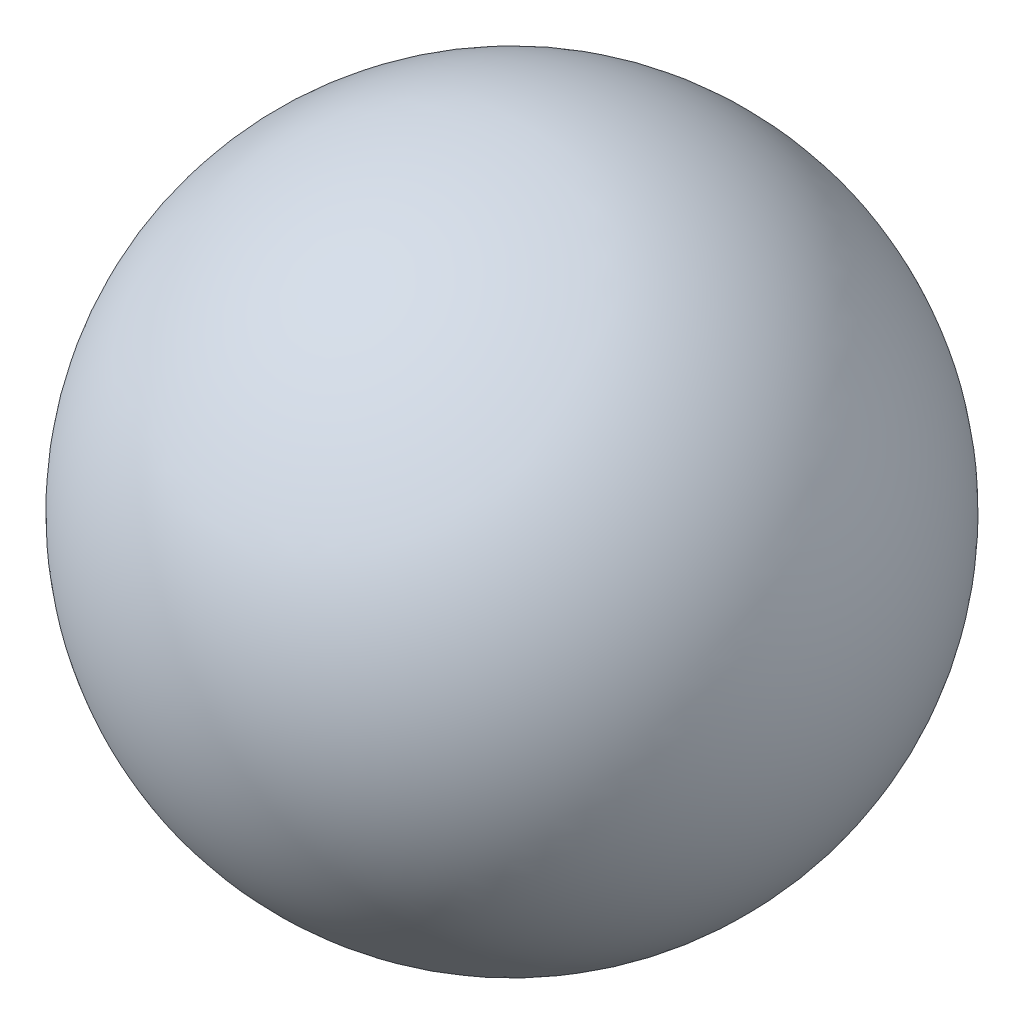
SolidWorks part; units mm, degrees
ref_plane "Plano frontal" through (0, 0, 0) normal (0, 0, 1) x (1, 0, 0)
ref_plane "Plano superior" through (0, 0, 0) normal (0, 1, 0) x (1, 0, 0)
ref_plane "Plano direito" through (0, 0, 0) normal (1, 0, 0) x (0, 0, -1)
sketch "Esboço1" plane through (0, 0, 0) normal (0, 1, 0) x (1, 0, 0)
  line L0 (0, 3.6028) -> (0, -5.4663) construction
  line L1 (0, 2.25) -> (0, -2.25)
  arc A0 (0, -2.25) -> (0, 2.25) centre (0, 0) ccw
revolve "Revolução1" add sketch "Esboço1" angle 360 about L0
ref_plane "Plano1" through (0, 1.75, 0) normal (0, 1, 0) x (1, 0, 0)
ref_axis "Eixo1" through (0, 2.475, 0) along (0, -1, 0)
